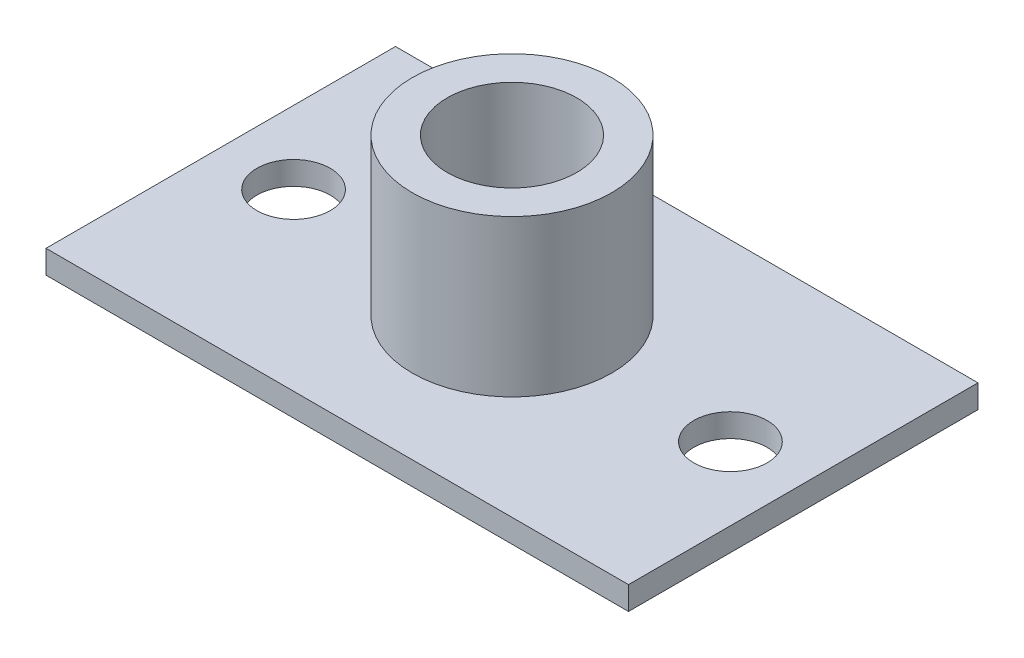
SolidWorks part; units mm, degrees
ref_plane "Front Plane" through (0, 0, 0) normal (0, 0, 1) x (1, 0, 0)
ref_plane "Top Plane" through (0, 0, 0) normal (0, 1, 0) x (1, 0, 0)
ref_plane "Right Plane" through (0, 0, 0) normal (1, 0, 0) x (0, 0, -1)
sketch "Sketch1" plane through (0, 0, 0) normal (0, 1, 0) x (1, 0, 0)
  line L0 (-25, 0) -> (8.56, 0) construction
  line L1 (-25, -15) -> (25, -15)
  line L2 (-25, -15) -> (-25, 15)
  line L3 (-25, 15) -> (25, 15)
  line L4 (25, -15) -> (25, 15)
  line L5 (-25, -15) -> (25, 15) construction
  line L6 (-25, 15) -> (25, -15) construction
  line L7 (8.56, 0) -> (0, 0) construction
  line L8 (0, 0) -> (-25, 0) construction
  line L9 (-12.5, 0) -> (-25, 0) construction
  line L10 (8.56, 0) -> (0, 0) construction
  line L11 (0, 0) -> (25, 0) construction
  line L12 (25, 0) -> (12.5, 0) construction
  circle A0 centre (0, 0) radius 5.56
  circle A1 centre (0, 0) radius 8.56
  circle A2 centre (-18.75, 0) radius 3.15
  circle A3 centre (18.75, 0) radius 3.15
  dimension "D1" = 3
  dimension "D2" = 17.12
  dimension "D3" = 11.12
  dimension "D4" = 50
  dimension "D5" = 30
extrude "Boss-Extrude1" add sketch "Sketch1" along normal blind 15.41 contours A1 A0 | A1 | A0 region at (-8.3179, 0, 0)
extrude "Boss-Extrude2" add sketch "Sketch1<3>" along normal blind 2 separate body contours L3 L4 L1 L2
sketch "Sketch1<3>" plane through (0, 0, 0) normal (0, 1, 0) x (1, 0, 0) same geometry as "Sketch1"
extrude "Cut-Extrude1" cut sketch "Sketch1<4>" along normal blind 2 contours A0
sketch "Sketch1<4>" plane through (0, 0, 0) normal (0, 1, 0) x (1, 0, 0) same geometry as "Sketch1"
extrude "Cut-Extrude2" cut sketch "Sketch1<5>" along normal blind 2 contours A2 | A3
sketch "Sketch1<5>" plane through (0, 0, 0) normal (0, 1, 0) x (1, 0, 0) same geometry as "Sketch1"
